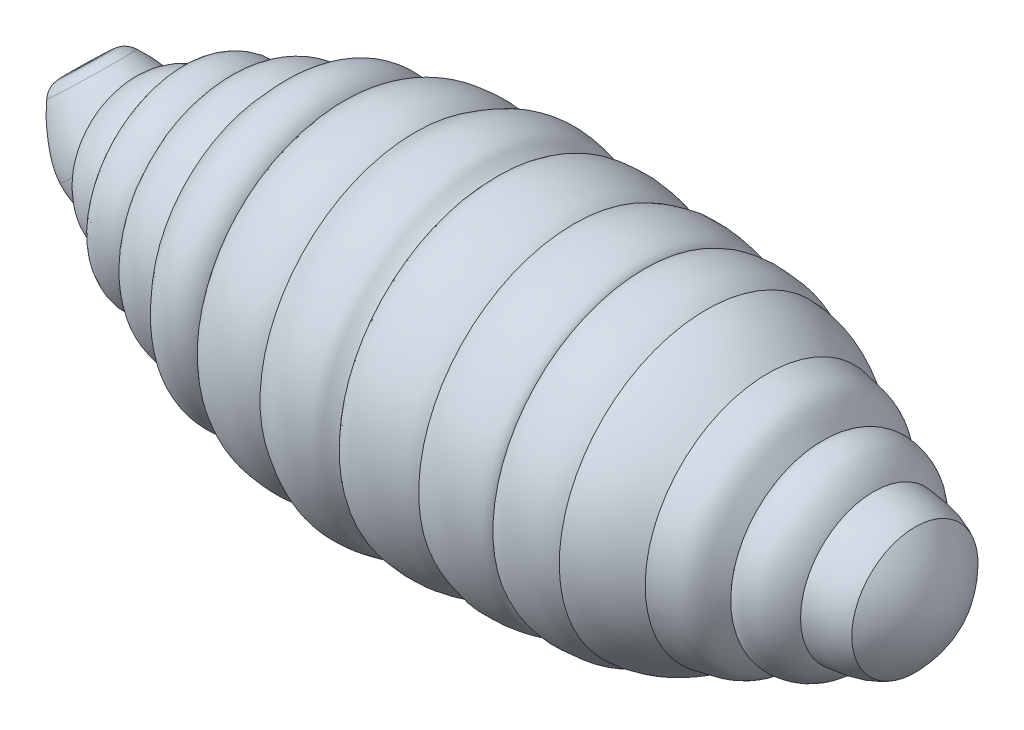
SolidWorks part; units mm, degrees
ref_plane "Piano frontale" through (0, 0, 0) normal (0, 0, 1) x (1, 0, 0)
ref_plane "Piano superiore" through (0, 0, 0) normal (0, 1, 0) x (1, 0, 0)
ref_plane "Piano destro" through (0, 0, 0) normal (1, 0, 0) x (0, 0, -1)
sketch "Schizzo1" plane through (0, 0, 0) normal (0, 0, 1) x (1, 0, 0)
  line L0 (-42, 20) -> (-42, -20)
  line L1 (50, -20) -> (-50, -20)
  line L2 (50, -20) -> (50, 20)
  line L3 (50, 20) -> (-50, 20)
  line L4 (-50, -20) -> (-50, 20)
  line L5 (50, -20) -> (-50, 20) construction
  line L6 (50, 20) -> (-50, -20) construction
  line L7 (-37, 20) -> (-37, -20)
  line L8 (-32, 20) -> (-32, -20)
  line L9 (-26, 20) -> (-26, -20)
  line L10 (-19, 20) -> (-19, -20)
  line L11 (-1, 20) -> (-1, -20)
  line L12 (16, 20) -> (16, -20)
  line L13 (23, 20) -> (23, -20)
  line L14 (30, 20) -> (30, -20)
  line L15 (36, 20) -> (36, -20)
  line L16 (42, 20) -> (42, -20)
  line L17 (-10, 20) -> (-10, -20)
  line L18 (8, 20) -> (8, -20)
  line L19 (-50, 0) -> (50, 0)
  ellipse E0 centre (0, 0) end of major axis (-50, 0) minor radius 20
  spline S0 degree 3 poles (-50, 0) (-49.8905, 1.5051) (-49.3637, 4.5063) (-46.5862, 6.5724) (-44.3813, 8.0424) (-42.8695, 8.2671) (-42, 8.281) knots 0 0 0 0 0.374016 0.653478 0.79096 1 1 1 1
  spline S1 degree 3 poles (-37, 8.6695) (-37.5687, 8.8384) (-38.6222, 8.8956) (-39.9275, 8.4387) (-41.0572, 7.8494) (-41.6676, 7.2527) (-42, 6.8939) knots 0 0 0 0 0.318968 0.548468 0.73563 1 1 1 1
  spline S2 degree 3 poles (-37, 8.6695) (-36.875, 9.4103) (-36.7553, 10.8606) (-35.5564, 11.4681) (-34.9943, 11.7037) (-34.3972, 11.7224) (-33.8464, 11.7326) (-33.3521, 11.6818) (-32.9353, 11.6253) (-32.4911, 11.488) (-32.1901, 11.3251) (-32, 11.2076) knots 0 0 0 0 0.382043 0.470299 0.56474 0.641238 0.723825 0.801483 0.854068 0.904002 1 1 1 1
  spline S3 degree 3 poles (-32, 11.2076) (-31.4639, 12.0956) (-30.5044, 13.3624) (-28.2234, 14.2014) (-26.8702, 13.9919) (-26, 13.9037) knots 0 0 0 0 0.447477 0.624963 1 1 1 1
  spline S4 degree 3 poles (-26, 13.9037) (-25.2519, 14.6966) (-24.2034, 16.1922) (-22.1097, 16.6702) (-20.365, 16.3824) (-19.3441, 15.5426) (-19, 14.7814) knots 0 0 0 0 0.396545 0.574716 0.715439 1 1 1 1
  spline S5 degree 3 poles (-19, 14.7814) (-18.8759, 16.0289) (-17.5747, 17.2884) (-15.5098, 18.0754) (-14.0239, 18.2272) (-12.1615, 18.393) (-10.7976, 18.0401) (-10, 17.5888) knots 0 0 0 0 0.324865 0.474838 0.616409 0.743386 1 1 1 1
  spline S6 degree 3 poles (-10, 17.5888) (-9.1776, 18.0865) (-7.7983, 19.007) (-5.5235, 19.318) (-3.9361, 19.0692) (-2.2892, 18.7529) (-1.6164, 17.8472) (-1, 17.5888) knots 0 0 0 0 0.297872 0.496695 0.687344 0.793867 1 1 1 1
  spline S7 degree 3 poles (-1, 17.5888) (-0.6144, 18.1042) (0.3337, 18.6326) (1.6528, 18.7238) (2.535, 18.7948) (3.2722, 18.7962) (3.8916, 18.7459) (4.4752, 18.6672) (4.9922, 18.5616) (5.5426, 18.4667) (6.1148, 18.2846) (6.6812, 18.1833) (7.3305, 17.9804) (7.7376, 17.7488) (8, 17.5888) knots 0 0 0 0 0.199993 0.323104 0.41462 0.479252 0.555247 0.610373 0.664793 0.721613 0.786226 0.85365 0.902782 1 1 1 1
  spline S8 degree 3 poles (8, 17.5888) (8.582, 17.8804) (9.44, 18.0528) (10.5082, 18.3341) (11.0619, 18.2977) (11.504, 18.2994) (11.8664, 18.3093) (12.2606, 18.2674) (12.6391, 18.2312) (12.9995, 18.1872) (13.4295, 18.1316) (14.0354, 18.0082) (14.9737, 17.8255) (15.7089, 17.5562) (16, 17.1728) knots 0 0 0 0 0.229373 0.317536 0.393856 0.427343 0.476844 0.524045 0.56982 0.613702 0.654707 0.725802 0.835934 1 1 1 1
  spline S9 degree 3 poles (16, 17.1728) (16.4092, 17.3969) (17.0185, 17.5895) (17.9071, 17.6388) (18.2047, 17.6824) (18.6077, 17.6809) (18.9515, 17.6412) (20.3136, 17.5549) (21.4096, 17.4389) (22.5448, 16.9224) (23, 16.648) knots 0 0 0 0 0.201152 0.294306 0.364002 0.381415 0.468436 0.545692 0.779325 1 1 1 1
  spline S10 degree 3 poles (23, 16.648) (25.621, 16.5633) (27.9044, 15.3074) (30, 13.9037) knots 0 0 0 0 1 1 1 1
  spline S11 degree 3 poles (30, 13.9037) (31.1983, 13.6198) (34.0789, 13.5061) (35.3498, 11.0047) (36, 10.0968) knots 0 0 0 0 0.529447 1 1 1 1
  spline S12 degree 3 poles (36, 10.0968) (36.1649, 10.4394) (36.6964, 10.8691) (37.7459, 11.0782) (38.6875, 10.8758) (39.7657, 10.5498) (40.8971, 9.6821) (41.6422, 8.8534) (42, 8.281) knots 0 0 0 0 0.152465 0.266191 0.427435 0.541586 0.725794 1 1 1 1
  spline S13 degree 3 poles (42, 8.281) (43.5956, 8.0954) (45.2531, 7.9607) (46.6889, 7.1571) knots 0 0 0 0 1 1 1 1
  spline S14 degree 3 poles (46.6889, 7.1571) (47.5097, 6.2998) (48.5437, 4.9767) (49.6957, 2.5341) (50.0033, 1.0418) (50, 0) knots 0 0 0 0 0.441872 0.616184 1 1 1 1
  point P0 (0, 0)
  dimension "D1" = 40
  dimension "D2" = 100
  dimension "D3" = 8
  dimension "D4" = 5
  dimension "D5" = 5
  dimension "D6" = 6
  dimension "D7" = 7
  dimension "D8" = 9
  dimension "D9" = 9
  dimension "D10" = 9
  dimension "D11" = 8
  dimension "D12" = 7
  dimension "D13" = 7
  dimension "D14" = 6
  dimension "D15" = 6
revolve "Rivoluzione4" add sketch "Schizzo1" angle 360 about L19 region at (-39.4136, 4.1818, 0) region at (-34.4568, 5.6902, 0) region at (-28.9147, 6.744, 0) region at (-22.4557, 7.9436, 0) region at (-14.4244, 8.8762, 0) region at (-5.4963, 9.356, 0) region at (3.4855, 9.2271, 0) region at (11.9891, 9.0184, 0) region at (19.482, 8.7169, 0) region at (26.3957, 7.851, 0) region at (32.8687, 6.4454, 0) region at (38.9027, 5.1907, 0) region at (45.4135, 3.5712, 0)
sketch "Schizzo3" plane through (-42, 0, 0) normal (-1, 0, 0) x (0, 0, 1)
  circle A0 centre (0, 0) radius 8.281
sketch "Schizzo4" plane through (0, 0, 0) normal (0, 1, 0) x (1, 0, 0)
  line L0 (-42, 8.281) -> (-42, -8.281) construction
  line L1 (-42, 8.281) -> (-42, -8.281)
  circle A0 centre (-42, 0) radius 8.281
  circle A1 centre (-42, 0) radius 6.5
  dimension "D1" = 13
revolve "Rivoluzione7" add sketch "Schizzo4" angle 360 about L1 region at (-44.7587, 0, 0)
sketch "Schizzo7" plane through (0, 0, 0) normal (0, 0, 1) x (1, 0, 0)
  line L0 (0, 0) -> (-49.9648, 0)
  line L1 (-49.9648, 0) -> (-49.9648, 6.0958)
  line L2 (-49.9648, 6.0958) -> (-41.8301, 10.6501)
  line L3 (-41.8301, 10.6501) -> (-42, 8.0929)
  line L4 (-42, 8.281) -> (-42, -8.281) construction
  line L5 (-42, 8.0929) -> (-42, 0)
  line L6 (-42, 0) -> (-48.9192, 0)
  line L7 (-48.9192, 0) -> (-42, 6.5)
  arc A0 (-42, 6.5) -> (-42, -6.5) centre (-42, 0) ccw construction
extrude "Taglio-Estrusione2" cut sketch "Schizzo7" against normal blind 10 and the other way blind 10 contours L0 L7 L5 L3 L2 L1 region at (-46.2838, 5.3586, 0)
sketch "Schizzo8" plane through (-22.9329, 24.4119, 0) normal (-0.6847, 0.7288, 0) x (0.7288, 0.6847, 0)
  circle A1 centre (-30.6113, 0) radius 4.4504
  circle A2 centre (-30.6113, 0) radius 4.4504
  dimension "D1" = 0
extrude "Estrusione-Estrusione1" add sketch "Schizzo8" along normal blind 3
fillet "Raccordo4" radius 2 1 edges at (-50.5414, 2.5922, 0)
sketch "Schizzo9" plane through (0, 0, 0) normal (0, 0, 1) x (1, 0, 0)
  line L0 (-47.2977, 5.6394) -> (-42, 0)
  line L1 (-45.5117, 7.3172) -> (-49.0837, 3.9616) construction
  line L2 (-42, 8.281) -> (-42, -8.281) construction
  line L3 (-42, 0) -> (-47.2977, 5.6394)
  line L4 (-42, 0) -> (-42, -6.5)
  arc A0 (-49.0837, 3.9616) -> (-49.172, 1.1346) centre (-47.7143, 2.5039) ccw construction
  arc A1 (-48.4873, 0.4057) -> (-42, -6.5) centre (-42, 0) ccw construction
  spline S0 degree 3 poles (-47.2977, 5.6394) (-47.8588, 5.0313) (-48.7647, 4.4083) (-49.7069, 3.2001) (-49.7212, 1.8635) (-49.2918, 0.3699) (-48.5225, -1.7966) (-46.8481, -5.0168) (-43.8822, -6.5394) (-42, -6.5) knots 0 0 0 0 0.14447 0.196446 0.261799 0.369333 0.472449 0.668415 1 1 1 1
revolve "Rivoluzione8" add sketch "Schizzo9" angle 360 about L0 region at (-45.628, -0.6741, 0)
